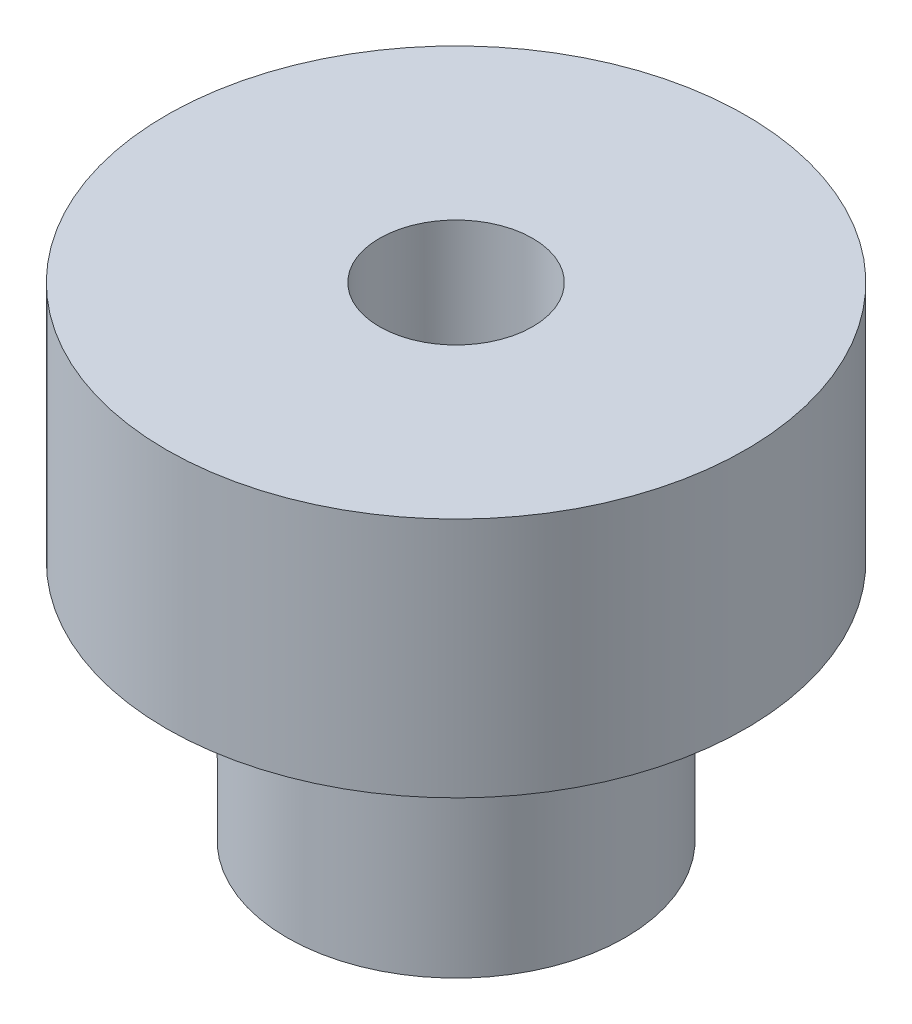
SolidWorks part; units mm, degrees
ref_plane "Front Plane" through (0, 0, 0) normal (0, 0, 1) x (1, 0, 0)
ref_plane "Top Plane" through (0, 0, 0) normal (0, 1, 0) x (1, 0, 0)
ref_plane "Right Plane" through (0, 0, 0) normal (1, 0, 0) x (0, 0, -1)
sketch "Sketch1" plane through (0, 0, 0) normal (0, 1, 0) x (1, 0, 0)
  circle A0 centre (0, 0) radius 6
  circle A1 centre (0, 0) radius 1.586
  dimension "D1" = 12
  dimension "D2" = 3.172
extrude "Boss-Extrude1" add sketch "Sketch1" along normal blind 5
sketch "Sketch2" plane through (0, 0, 0) normal (0, -1, 0) x (1, 0, 0)
  circle A0 centre (0, 0) radius 3.5
  circle A1 centre (0, 0) radius 1.586
  circle A2 centre (0, 0) radius 1.586 construction
  dimension "D1" = 7
extrude "Boss-Extrude2" add sketch "Sketch2" along normal blind 5
sketch "Sketch3" plane through (0, 0, 0) normal (1, 0, 0) x (0, 0, -1)
  line L0 (0, 0) -> (0, -5) construction
  line L1 (-3.5, -5) -> (3.5, -5) construction
  line L2 (-3.5, -2.5) -> (3.5, -2.5) construction
  line L3 (3.5, -5) -> (3.5, 0) construction
  circle A0 centre (0, -2.5) radius 1.25
  point P10 (0, -2.5)
  dimension "D1" = 2.5
extrude "Cut-Extrude1" cut sketch "Sketch3" against normal blind 10
